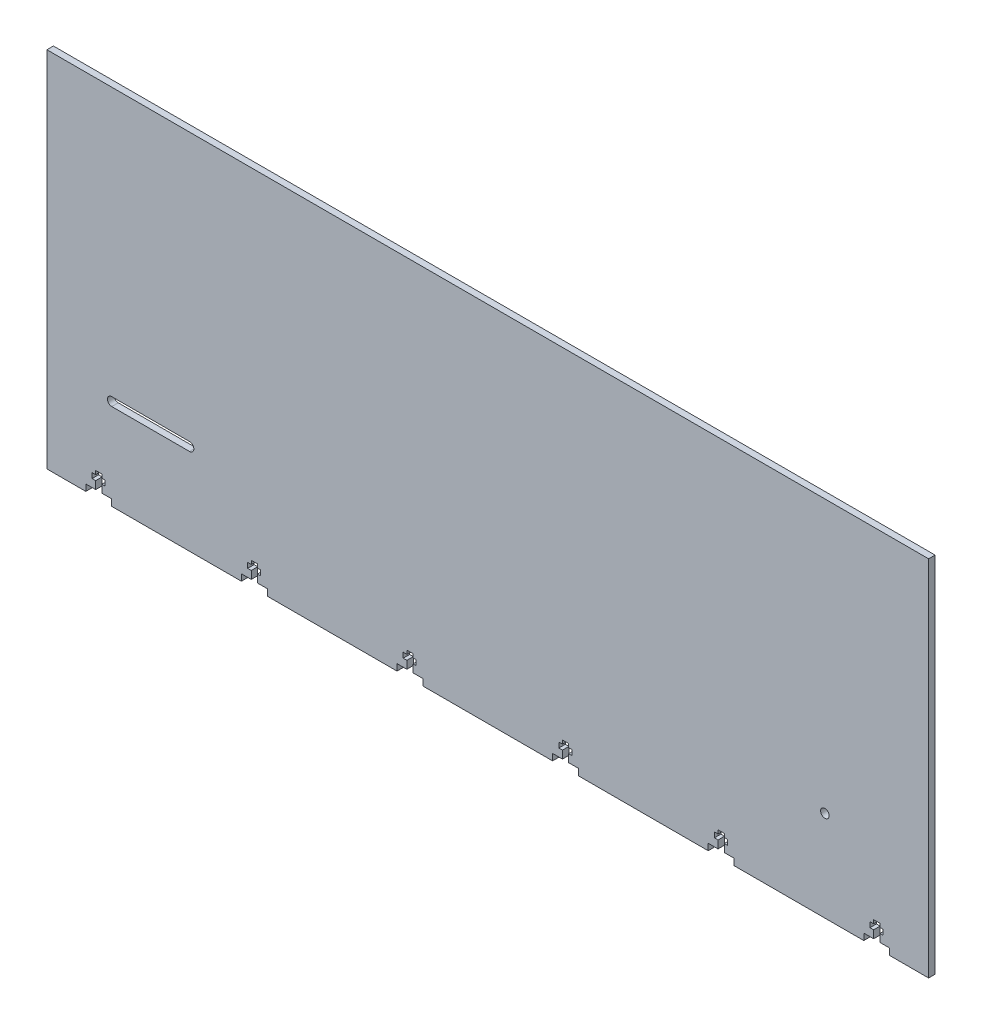
SolidWorks part; units mm, degrees
ref_plane "Front Plane" through (0, 0, 0) normal (0, 0, 1) x (1, 0, 0)
ref_plane "Top Plane" through (0, 0, 0) normal (0, 1, 0) x (1, 0, 0)
ref_plane "Right Plane" through (0, 0, 0) normal (1, 0, 0) x (0, 0, -1)
sketch "Sketch1" plane through (0, 0, 0) normal (0, 0, 1) x (1, 0, 0)
  line L1 (0, 0) -> (431.8, 0)
  line L2 (0, 0) -> (0, 177.8)
  line L3 (0, 177.8) -> (431.8, 177.8)
  line L4 (431.8, 0) -> (431.8, 177.8)
  dimension "D1" = 431.8
  dimension "D2" = 177.8
extrude "Boss-Extrude1" add sketch "Sketch1" along normal blind 3.175
sketch "Sketch2" plane through (0, 0, 3.175) normal (0, 0, 1) x (1, 0, 0)
  line L0 (31.75, 44.45) -> (69.85, 44.45) construction
  line L1 (31.75, 46.55) -> (69.85, 46.55)
  line L2 (31.75, 42.35) -> (69.85, 42.35)
  line L3 (0, 0) -> (431.8, 0) construction
  line L5 (0, 177.8) -> (0, 0) construction
  arc A0 (31.75, 46.55) -> (31.75, 42.35) centre (31.75, 44.45) ccw
  arc A1 (69.85, 42.35) -> (69.85, 46.55) centre (69.85, 44.45) ccw
  point P2 (50.8, 44.45)
  dimension "D2" = 38.1
  dimension "D1" = 4.2
  dimension "D3" = 44.45
  dimension "D4" = 50.8
extrude "Cut-Extrude1" cut sketch "Sketch2" against normal blind 3.175
ref_plane "Plane1" through (215.9, 0, 0) normal (-1, 0, 0) x (0, 0, 1)
sketch "Sketch6" plane through (0, 0, 3.175) normal (0, 0, 1) x (1, 0, 0)
  line L2 (19.05, 0) -> (31.75, 0)
  line L3 (19.05, 0) -> (19.05, 3.175)
  line L4 (19.05, 3.175) -> (23.876, 3.175)
  line L5 (31.75, 0) -> (31.75, 3.175)
  line L6 (0, 177.8) -> (0, 0) construction
  line L7 (23.876, 3.175) -> (23.876, 6.985)
  line L8 (23.876, 11.303) -> (26.924, 11.303)
  line L9 (26.924, 3.175) -> (26.924, 6.985)
  line L10 (23.876, 9.525) -> (23.876, 11.303)
  line L11 (22.098, 9.525) -> (23.876, 9.525)
  line L12 (22.098, 9.525) -> (22.098, 6.985)
  line L13 (22.098, 6.985) -> (23.876, 6.985)
  line L14 (28.448, 9.525) -> (28.448, 6.985)
  line L15 (26.924, 9.525) -> (28.448, 9.525)
  line L16 (26.924, 9.525) -> (26.924, 11.303)
  line L17 (26.924, 6.985) -> (28.448, 6.985)
  line L18 (26.924, 3.175) -> (31.75, 3.175)
  line L19 (0, 0) -> (431.8, 0) construction
  point P8 (25.4, 11.303)
  dimension "D1" = 3.175
  dimension "D2" = 12.7
  dimension "D3" = 8.128
  dimension "D4" = 3.048
  dimension "D5" = 6.35
  dimension "D6" = 2.54
  dimension "D7" = 6.35
  dimension "D8" = 1.778
  dimension "D9" = 6.35
  dimension "D10" = 19.05
extrude "Cut-Extrude2" cut sketch "Sketch6" against normal blind 3.175
pattern_linear "LPattern1" count 6 spacing 76.2 along (1, 0, 0) of "Cut-Extrude2"
sketch "Sketch7" plane through (0, 0, 3.175) normal (0, 0, 1) x (1, 0, 0)
  line L0 (431.8, 0) -> (431.8, 177.8) construction
  line L2 (381, 44.45) -> (431.8, 44.45) construction
  circle A0 centre (381, 44.45) radius 2.1
  dimension "D1" = 4.2
  dimension "D2" = 50.8
  dimension "D3" = 44.45
extrude "Cut-Extrude3" cut sketch "Sketch7" against normal blind 3.175
